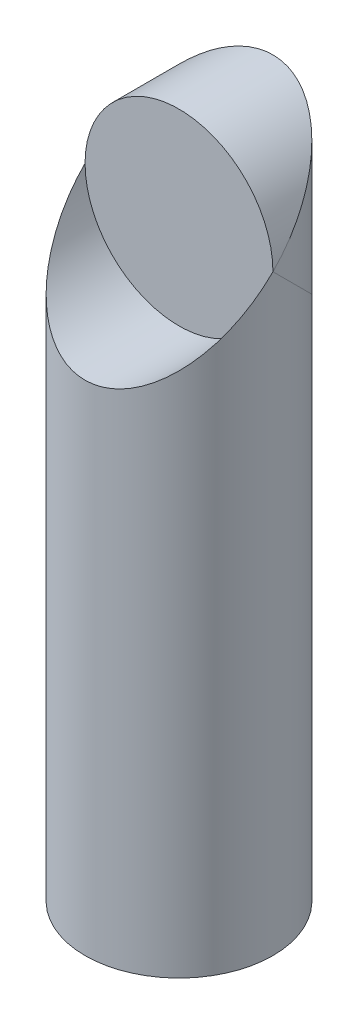
SolidWorks part; units mm, degrees
ref_plane "Front Plane" through (0, 0, 0) normal (0, 0, 1) x (1, 0, 0)
ref_plane "Top Plane" through (0, 0, 0) normal (0, 1, 0) x (1, 0, 0)
ref_plane "Right Plane" through (0, 0, 0) normal (1, 0, 0) x (0, 0, -1)
sketch "Sketch1" plane through (0, 0, 0) normal (0, 1, 0) x (1, 0, 0)
  line L0 (-53.2343, -13.9682) -> (45.2465, -31.333) construction
  circle A0 centre (0, 0) radius 23
extrude "Boss-Extrude1" add sketch "Sketch1" along normal blind 145
ref_point "Point1"
sketch "Sketch2" plane through (0, 0, 0) normal (0, 0, 1) x (1, 0, 0)
  circle A0 centre (0, 145) radius 23
extrude "Cut-Extrude1" cut sketch "Sketch2<4>" against normal through all both and the other way through all
sketch "Sketch2<4>" plane through (0, 0, 0) normal (0, 0, 1) x (1, 0, 0) same geometry as "Sketch2"
extrude "Boss-Extrude3" add sketch "Sketch2" against normal up to surface separate body contours A0 up to face at (0, 0, 23)
sketch3d "3DSketch1"
  line L0 (0, 145, 0) -> (163.4635, 145, 0) construction
  line L1 (0, 145, 0) -> (0, 145, 66.0008)
  line L2 (0, 0, 0) -> (0, 241.2858, 0) construction
